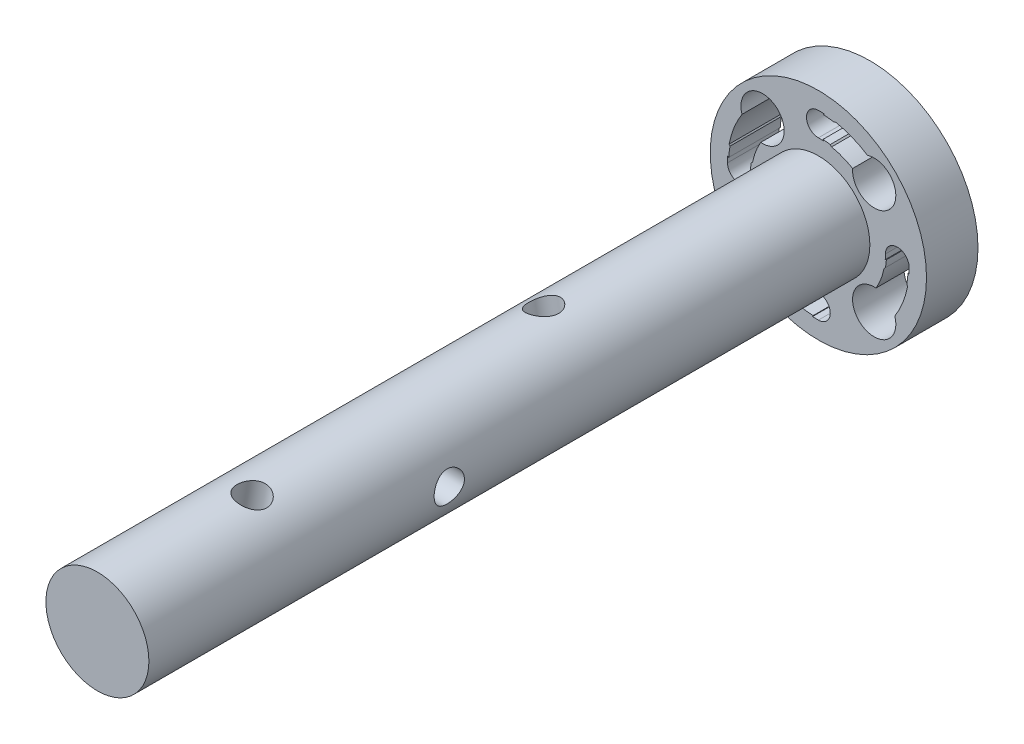
SolidWorks part; units mm, degrees
ref_plane "Front Plane" through (0, 0, 0) normal (0, 0, 1) x (1, 0, 0)
ref_plane "Top Plane" through (0, 0, 0) normal (0, 1, 0) x (1, 0, 0)
ref_plane "Right Plane" through (0, 0, 0) normal (1, 0, 0) x (0, 0, -1)
sketch "Sketch1" plane through (0, 0, 0) normal (0, 0, 1) x (1, 0, 0)
  circle A0 centre (0, 0) radius 4.7625
  circle A1 centre (0, 0) radius 10
  circle A2 centre (0, 0) radius 3.175
  circle A5 centre (0, 0) radius 3.175
  circle A7 centre (0, 0) radius 3.175
  circle A9 centre (0, 0) radius 3.175
  point P19 (0, 0)
  dimension "D1" = 9.525
  dimension "D2" = 20
  dimension "D3" = 6.35
  dimension "D6" = 4
extrude "Boss-Extrude1" add sketch "Sketch1" along normal blind 66.675 contours A0
extrude "Boss-Extrude2" add sketch "Sketch1<4>" against normal blind 4.7625 contours A1 A0 | A0 A2 region at (-4.6278, 0, 0) region at (-9.7172, 0, 0)
sketch "Sketch1<4>" plane through (0, 0, 0) normal (0, 0, 1) x (1, 0, 0) same geometry as "Sketch1"
fillet "Fillet1" radius 3.175 1 edges at (3.175, 0, 0)
sketch "Sketch2" plane through (0, 0, 0) normal (0, 1, 0) x (1, 0, 0)
  line L0 (-4.7625, -66.675) -> (4.7625, -66.675) construction
  line L1 (0, -66.675) -> (0, -53.1812) construction
  line L2 (0, -53.1812) -> (0, -38.8937) construction
  line L3 (0, -38.8937) -> (0, -24.6062) construction
  dimension "D2" = 13.4937
  dimension "D1" = 14.2875
  dimension "D3" = 14.2875
sketch "Sketch3" plane through (0, 0, 0) normal (1, 0, 0) x (0, 0, -1)
  circle A0 centre (-38.8937, 0) radius 1.4
  dimension "D1" = 2.8
extrude "Cut-Extrude2" cut sketch "Sketch3" against normal through all both and the other way through all
ref_plane "Plane1" through (0, 0, 0) normal (0.1736, 0.9848, 0) x (0, 0, -1)
ref_plane "Plane2" through (0, 0, 0) normal (-0.1736, 0.9848, 0) x (0, 0, -1)
sketch "Sketch4" plane through (0, 0, 0) normal (0.1736, 0.9848, 0) x (0, 0, -1)
  circle A0 centre (-53.1812, 0) radius 1.4
  dimension "D1" = 2.8
extrude "Cut-Extrude3" cut sketch "Sketch4" against normal through all both and the other way through all
sketch "Sketch5" plane through (0, 0, 0) normal (-0.1736, 0.9848, 0) x (0, 0, -1)
  circle A0 centre (-24.6062, 0) radius 1.4
  dimension "D1" = 2.8
extrude "Cut-Extrude4" cut sketch "Sketch5" against normal through all both and the other way through all
sketch "Sketch6" plane through (0, 0, -4.7625) normal (0, 0, -1) x (-1, 0, 0)
  line L0 (0, 7.3) -> (0, 0) construction
  line L1 (0, 0) -> (-5.1619, 5.1619) construction
  arc A0 (0, 6.2) -> (0, 8.4) centre (0, 7.3) ccw
  arc A4 (-4.5448, 7.0643) -> (-3.1689, 5.329) centre (-5.1619, 5.1619) ccw
  arc A5 (0, 6.2) -> (-3.1689, 5.329) centre (0, 0) ccw
  arc A6 (0, 8.4) -> (-4.5448, 7.0643) centre (0, 0) ccw
  point P12 (0, 0)
  dimension "D3" = 2.2
  dimension "D5" = 4
  dimension "D1" = 7.3
  dimension "D4" = 45
extrude "Cut-Extrude5" cut sketch "Sketch6" against normal through all
sketch "Sketch7" plane through (0, 0, -4.7625) normal (0, 0, -1) x (-1, 0, 0)
  line L0 (0, 0) -> (-2.5511, 14.4681)
  line L1 (0, 7.3) -> (0, 0) construction
  line L2 (-0.8034, 8.9211) -> (0, 7.3)
  line L3 (0, 7.3) -> (-0.5451, 6.0005)
  line L4 (-2.9919, 9.1141) -> (0, 7.3)
  line L5 (0, 7.3) -> (-2.099, 5.1977)
  arc A0 (0, 8.4) -> (-0.4884, 8.2856) centre (0, 7.3) ccw
  arc A1 (0, 6.2) -> (-3.1689, 5.329) centre (0, 0) ccw construction
  arc A4 (0, 8.3) -> (-4.4907, 6.9802) centre (0, 0) ccw
  arc A5 (-0.4884, 8.2856) -> (-1.4413, 8.1739) centre (0, 0) ccw
  arc A6 (0, 8.4) -> (-4.5448, 7.0643) centre (0, 0) ccw construction
  arc A7 (0, 6.3) -> (-3.22, 5.415) centre (0, 0) ccw
  arc A8 (-0.4255, 6.2856) -> (-1.094, 6.2043) centre (0, 0) ccw
  arc A9 (0, 6.2) -> (-1.2191, 6.079) centre (0, 0) ccw
  arc A10 (-0.4255, 6.2856) -> (0, 6.2) centre (0, 7.3) ccw
  arc A11 (0, 8.4) -> (-1.57, 8.252) centre (0, 0) ccw
  arc M8 (0, 6.2) -> (-3.1689, 5.329) centre (0, 0) ccw
  arc M10 (-4.5448, 7.0643) -> (0, 8.4) centre (0, 0) cw
  dimension "D3" = 10
  dimension "D1" = 0.1
  dimension "D2" = 0.1
extrude "Boss-Extrude3" add sketch "Sketch7" against normal up to surface (4.7625 mm away) contours A10 A8 L0 M8 | A5 A0 L0 M10 | L0 L5 M8 | L4 L0 M10 region at (0.7668, 6.2008, -4.7625) region at (1.1298, 6.1299, -4.7625) region at (1.49, 8.2328, -4.7625) region at (0.9822, 8.2873, -4.7625) up to face at (2.4102, 6.3142, 0)
pattern_circular "CirPattern1" count 4 over 360 about axis through (0, 0, -4.7625) along (0, 0, 1) of "Cut-Extrude5", "Boss-Extrude3"
equation "\"normtol\" = 0.01in"
equation "\"loosetol\" = 0.02in"
equation "\"tighttol\" = 0.005in"
equation "\"Fry height\"= 0.5in"
equation "\"Fry spacing\"= 0.5625in"
equation "\"Potato width\"= \"Fry spacing\" * 4"
equation "\"Potato length\"= 80mm"
equation "\"top robot surface separation\" = 0.6875"
equation "\"D2@Sketch2\"=1/4+\"Fry spacing\"/2"
equation "\"D1@Sketch3\"=2.8mm"
equation "\"D1@Sketch2\"=\"Fry spacing\""
equation "\"D3@Sketch2\"=\"Fry spacing\""
equation "\"D1@Sketch4\"=2.8mm"
equation "\"D1@Sketch5\"=2.8mm"
equation "\"D1@Sketch6\"=7.3mm"
equation "\"D3@Sketch6\"=2.2mm"
equation "\"D5@Sketch6\"=4mm"
equation "\"D2@Sketch1\"=20mm"
equation "\"D1@Sketch7\"=0.1mm"
equation "\"D2@Sketch7\"=0.1mm"
